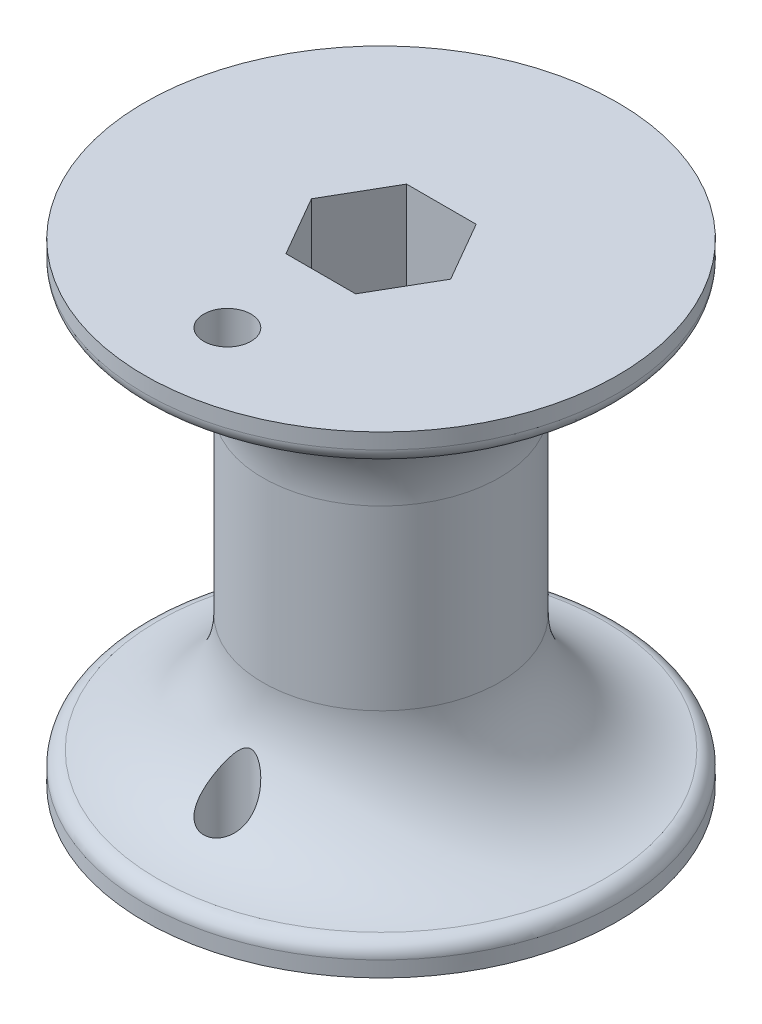
SolidWorks part; units mm, degrees
ref_plane "Front Plane" through (0, 0, 0) normal (0, 0, 1) x (1, 0, 0)
ref_plane "Top Plane" through (0, 0, 0) normal (0, 1, 0) x (1, 0, 0)
ref_plane "Right Plane" through (0, 0, 0) normal (1, 0, 0) x (0, 0, -1)
sketch "Sketch1" plane through (0, 0, 0) normal (1, 0, 0) x (0, 0, -1)
  line L0 (0, 0) -> (0, 25.4)
  line L1 (0, 25.4) -> (25.4, 25.4)
  line L2 (25.4, 25.4) -> (25.4, 22.225)
  line L4 (12.7, 9.525) -> (12.7, 0)
  line L5 (12.7, 0) -> (0, 0)
  arc A0 (12.7, 9.525) -> (25.4, 22.225) centre (25.4, 9.525) cw
  dimension "D1" = 25.4
  dimension "D3" = 3.175
  dimension "D4" = 12.7
  dimension "D5" = 25.4
  dimension "D6" = 9.525
revolve "Revolve1" add sketch "Sketch1" angle 360 about L0
mirror "Mirror1" about plane through (0, 0, -12.7) normal (0, -1, 0) of "Revolve1"
sketch "Sketch2" plane through (0, 25.4, 0) normal (0, 1, 0) x (1, 0, 0)
  line L7 (-3.7395, -6.477) -> (3.7395, -6.477)
  line L8 (3.7395, -6.477) -> (7.479, 0)
  line L9 (7.479, 0) -> (3.7395, 6.477)
  line L10 (3.7395, 6.477) -> (-3.7395, 6.477)
  line L11 (-3.7395, 6.477) -> (-7.479, 0)
  line L12 (-7.479, 0) -> (-3.7395, -6.477)
  circle A0 centre (0, 0) radius 6.477 construction
  circle A1 centre (0, -16.51) radius 2.54
  circle A2 centre (0, 0) radius 25.4 construction
  dimension "D2" = 5.08
  dimension "D1" = 12.954
  dimension "0." = 16.51
extrude "Cut-Extrude1" cut sketch "Sketch2" against normal through all
fillet "Fillet1" radius 1.5875 2 edges at (0, -22.225, -25.4) (0, 22.225, -25.4)
